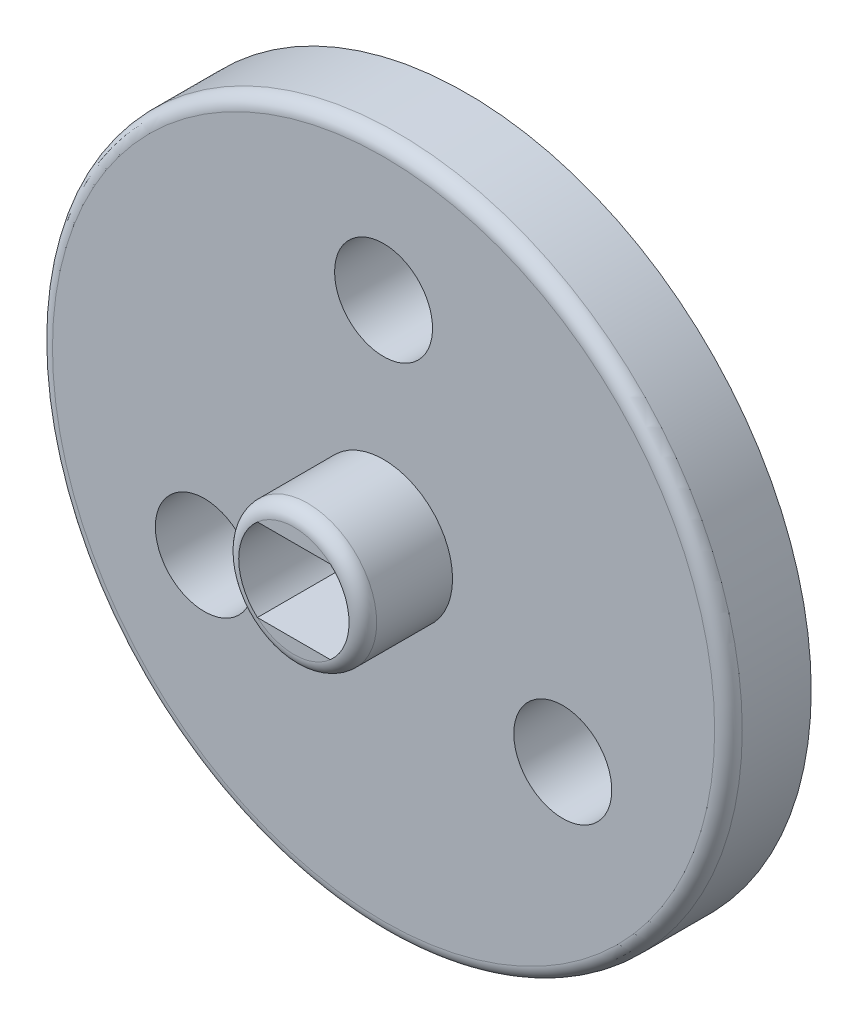
SolidWorks part; units mm, degrees
ref_plane "Ebene vorne" through (0, 0, 0) normal (0, 0, 1) x (1, 0, 0)
ref_plane "Ebene oben" through (0, 0, 0) normal (0, 1, 0) x (1, 0, 0)
ref_plane "Ebene rechts" through (0, 0, 0) normal (1, 0, 0) x (0, 0, -1)
sketch "Skizze1" plane through (0, 0, 0) normal (1, 0, 0) x (0, 0, -1)
  line L1 (96.5, 25) -> (96.5, 0) construction
  line L2 (90.5, 25) -> (90.5, 0) construction
  line L3 (0, 25) -> (99, 25) construction
  line L5 (96.5, 25) -> (96.5, 0)
  line L6 (90.5, 25) -> (90.5, 5)
  line L7 (90.5, 25) -> (96.5, 25)
  line L8 (84, 4) -> (84, 0) construction
  line L10 (84, 4) -> (84, 0)
  line L12 (0, 0) -> (99, 0) construction
  line L13 (84, 0) -> (96.5, 0)
  line L14 (84, 5) -> (84, 4) construction
  line L15 (90.5, 5) -> (84, 5) construction
  line L16 (84, 5) -> (84, 4)
  line L17 (90.5, 5) -> (84, 5)
revolve "Rotation1" add sketch "Skizze1" angle 360 about L13
sketch "Skizze2" plane through (0, 0, -96.5) normal (0, 0, -1) x (-1, 0, 0)
  line L0 (0, 0) -> (25, 0) construction
  line L1 (0, 0) -> (-450, 0) construction
  line L2 (2.6458, 3) -> (-2.6458, 3) construction
  line L3 (0, 0) -> (4, 0)
  line L4 (0, 0) -> (-4, 0)
  line L5 (2.6458, 3) -> (-2.6458, 3)
  arc A1 (-2.6458, 3) -> (-4, 0) centre (0, 0) ccw construction
  arc A2 (4, 0) -> (2.6458, 3) centre (0, 0) ccw construction
  arc A3 (-2.6458, 3) -> (-4, 0) centre (0, 0) ccw
  arc A4 (4, 0) -> (2.6458, 3) centre (0, 0) ccw
extrude "Schnitt-Linear austragen1" cut sketch "Skizze2" against normal through all
mirror "Spiegeln1" about plane through (0, 0, -84) normal (0, -1, 0) of "Schnitt-Linear austragen1"
sketch "Skizze3" plane through (0, 0, -96.5) normal (0, 0, -1) x (-1, 0, 0)
  circle A0 centre (0, 0) radius 15 construction
  point P4 (0, 15)
hole_wizard "Ø7.1 (7.1) Durchmesser Bohrung1" positions "Skizze3" profile "Skizze4" hole size "Ø7.1" standard "DIN"
sketch "Skizze4" plane through (0, 15, -96.5) normal (1, 0, 0) x (0, 1, 0)
  line L0 (0, 0) -> (0, 10.6331)
  line L1 (0, 10.6331) -> (3.55, 8.5)
  line L2 (3.55, 8.5) -> (3.55, 0)
  line L5 (3.55, 0) -> (0, 0)
  line L10 (0, 10.6331) -> (-3.55, 8.5) construction
  line L11 (0, -6.35) -> (0, 107.95) construction
  dimension "Bohrerdurchmesser" = 7.1
  dimension "Bohrungstiefe" = 8.5
  dimension "Spitzenwinkel" = 118
pattern_circular "Kreismuster1" count 3 over 360 of "Ø7.1 (7.1) Durchmesser Bohrung1" reverse direction yes
fillet "Verrundung1" radius 1 2 edges at (5, 0, -84) (25, 0, -90.5)
